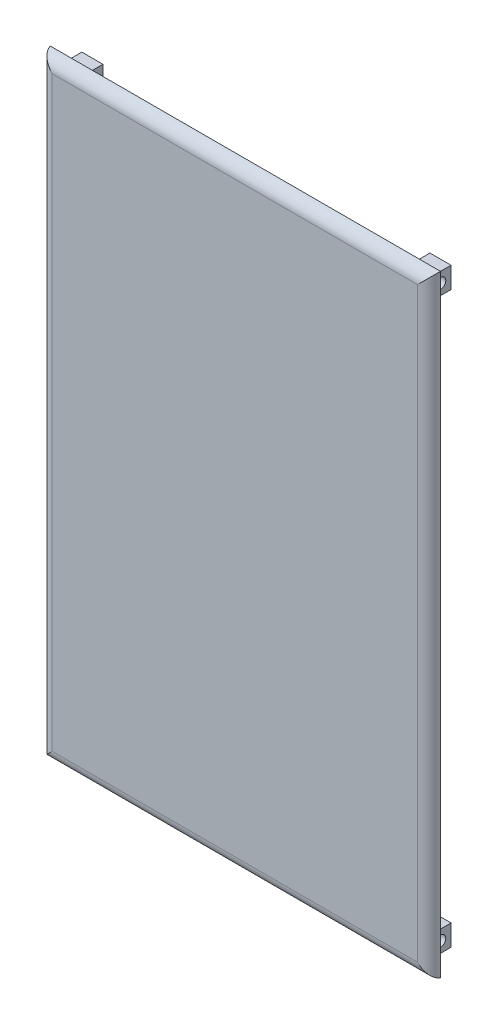
SolidWorks part; units mm, degrees
ref_plane "Front Plane" through (0, 0, 0) normal (0, 0, 1) x (1, 0, 0)
ref_plane "Top Plane" through (0, 0, 0) normal (0, 1, 0) x (1, 0, 0)
ref_plane "Right Plane" through (0, 0, 0) normal (1, 0, 0) x (0, 0, -1)
sketch "Sketch3" plane through (0, 0, 0) normal (0, 0, 1) x (1, 0, 0)
  line L1 (0, 184.15) -> (117.475, 184.15)
  line L2 (0, 184.15) -> (0, 0)
  line L3 (0, 0) -> (117.475, 0)
  line L4 (117.475, 184.15) -> (117.475, 0)
  dimension "D1" = 184.15
  dimension "D2" = 117.475
extrude "Boss-Extrude2" add sketch "Sketch3" along normal blind 3.175
fillet "Fillet1" radius 3.81 4 edges at (58.7375, 0, 3.175) (117.475, 92.075, 3.175) (0, 92.075, 3.175) (58.7375, 184.15, 3.175)
sketch "Sketch13" plane through (0, 0, 0) normal (0, 0, -1) x (-1, 0, 0)
  line L0 (-117.475, 0) -> (-117.475, 184.15) construction
  line L1 (-114.3, 180.975) -> (-3.175, 180.975)
  line L2 (-114.3, 180.975) -> (-114.3, 3.175)
  line L3 (-114.3, 3.175) -> (-3.175, 3.175)
  line L4 (-3.175, 180.975) -> (-3.175, 3.175)
  line L5 (0, 0) -> (-117.475, 0) construction
  line L7 (-112.7125, 179.3875) -> (-4.7625, 179.3875)
  line L8 (-112.7125, 179.3875) -> (-112.7125, 4.7625)
  line L9 (-112.7125, 4.7625) -> (-4.7625, 4.7625)
  line L10 (-4.7625, 179.3875) -> (-4.7625, 4.7625)
  dimension "D1" = 177.8
  dimension "D2" = 111.125
  dimension "D3" = 3.175
  dimension "D4" = 3.175
  dimension "D5" = 174.625
  dimension "D6" = 107.95
  dimension "D7" = 4.7625
  dimension "D8" = 4.7625
extrude "Boss-Extrude4" add sketch "Sketch13" along normal blind 3.175
sketch "Sketch14" plane through (0, 0, 0) normal (0, 0, -1) x (-1, 0, 0)
  line L1 (-114.3, 180.975) -> (-107.95, 180.975)
  line L2 (-114.3, 180.975) -> (-114.3, 174.625)
  line L3 (-114.3, 174.625) -> (-107.95, 174.625)
  line L4 (-107.95, 180.975) -> (-107.95, 174.625)
  line L5 (-3.175, 180.975) -> (-9.525, 180.975)
  line L6 (-3.175, 180.975) -> (-3.175, 174.625)
  line L7 (-3.175, 174.625) -> (-9.525, 174.625)
  line L8 (-9.525, 180.975) -> (-9.525, 174.625)
  line L9 (-114.3, 3.175) -> (-107.95, 3.175)
  line L10 (-114.3, 3.175) -> (-114.3, 9.525)
  line L11 (-114.3, 9.525) -> (-107.95, 9.525)
  line L12 (-107.95, 3.175) -> (-107.95, 9.525)
  line L13 (-3.175, 3.175) -> (-9.525, 3.175)
  line L14 (-3.175, 3.175) -> (-3.175, 9.525)
  line L15 (-3.175, 9.525) -> (-9.525, 9.525)
  line L16 (-9.525, 3.175) -> (-9.525, 9.525)
  dimension "D1" = 6.35
  dimension "D2" = 6.35
  dimension "D3" = 6.35
  dimension "D4" = 6.35
  dimension "D5" = 6.35
  dimension "D6" = 6.35
extrude "Boss-Extrude5" add sketch "Sketch14" along normal blind 6.35
fillet "Fillet9" radius 0.381 20 edges at (58.7375, 179.3875, 0) (4.7625, 92.075, 0) (58.7375, 4.7625, 0) (112.7125, 92.075, 0) (107.95, 179.3875, -1.5875) (107.95, 177.0062, 0) (110.3312, 174.625, 0) (112.7125, 174.625, -1.5875) (9.525, 179.3875, -1.5875) (9.525, 177.0062, 0) (7.1437, 174.625, 0) (4.7625, 174.625, -1.5875) (4.7625, 9.525, -1.5875) (7.1437, 9.525, 0) (9.525, 7.1437, 0) (9.525, 4.7625, -1.5875) (107.95, 4.7625, -1.5875) (107.95, 7.1437, 0) (110.3312, 9.525, 0) (112.7125, 9.525, -1.5875)
sketch "Sketch15" plane through (114.3, 0, 0) normal (1, 0, 0) x (0, 0, -1)
  line L0 (0, 180.975) -> (0, 3.175) construction
  line L1 (6.35, 3.175) -> (0, 3.175) construction
  line L2 (6.35, 9.525) -> (6.35, 3.175) construction
  line L4 (6.35, 180.975) -> (0, 180.975) construction
  circle A0 centre (3.175, 177.8) radius 1.5875
  circle A1 centre (3.175, 6.35) radius 1.5875
  circle A2 centre (3.175, 6.35) radius 1.5875
  dimension "D2" = 3.175
  dimension "D6" = 3.175
  dimension "D1" = 3.175
  dimension "D3" = 3.175
  dimension "D4" = 3.175
  dimension "D5" = 3.175
extrude "Cut-Extrude9" cut sketch "Sketch15" against normal blind 6.35 contours A1 | A0 region at (114.3, 177.8, -3.175) region at (114.3, 6.35, -3.175)
sketch "Sketch16" plane through (3.175, 0, 0) normal (-1, 0, 0) x (0, 0, 1)
  line L0 (-6.35, 174.625) -> (-6.35, 180.975) construction
  line L1 (-6.35, 180.975) -> (0, 180.975) construction
  line L2 (-6.35, 3.175) -> (-6.35, 9.525) construction
  line L3 (-6.35, 3.175) -> (0, 3.175) construction
  circle A0 centre (-3.175, 177.8) radius 1.5875
  circle A1 centre (-3.175, 6.35) radius 1.5875
  dimension "D3" = 3.175
  dimension "D6" = 3.175
  dimension "D1" = 3.175
  dimension "D2" = 3.175
  dimension "D4" = 3.175
  dimension "D5" = 3.175
extrude "Cut-Extrude10" cut sketch "Sketch16" against normal blind 6.35
sketch "Sketch17" plane through (0, 0, 0) normal (0, 0, -1) x (-1, 0, 0)
  line L0 (-9.906, 179.3875) -> (-107.569, 179.3875) construction
  line L1 (-103.3145, 177.8) -> (-101.727, 177.8)
  line L2 (-103.3145, 177.8) -> (-103.3145, 120.65)
  line L3 (-103.3145, 120.65) -> (-101.727, 120.65)
  line L4 (-101.727, 177.8) -> (-101.727, 120.65)
  line L5 (-15.748, 177.8) -> (-14.1605, 177.8)
  line L6 (-15.748, 177.8) -> (-15.748, 120.65)
  line L7 (-15.748, 120.65) -> (-14.1605, 120.65)
  line L8 (-14.1605, 177.8) -> (-14.1605, 120.65)
  line L9 (-112.7125, 9.906) -> (-112.7125, 174.244) construction
  line L10 (-4.7625, 9.906) -> (-4.7625, 174.244) construction
  dimension "D1" = 57.15
  dimension "D2" = 1.5875
  dimension "D3" = 1.5875
  dimension "D4" = 57.15
  dimension "D5" = 1.5875
  dimension "D6" = 1.5875
  dimension "D7" = 9.398
  dimension "D8" = 9.398
extrude "Boss-Extrude6" add sketch "Sketch17" along normal blind 4.7625
sketch "Sketch18" plane through (0, 0, 0) normal (0, 0, -1) x (-1, 0, 0)
  line L1 (-103.3145, 120.396) -> (-101.727, 120.396)
  line L2 (-103.3145, 120.396) -> (-103.3145, 63.246)
  line L3 (-103.3145, 63.246) -> (-101.727, 63.246)
  line L4 (-101.727, 120.396) -> (-101.727, 63.246)
  line L5 (-15.748, 120.396) -> (-14.1605, 120.396)
  line L6 (-15.748, 120.396) -> (-15.748, 63.246)
  line L7 (-15.748, 63.246) -> (-14.1605, 63.246)
  line L8 (-14.1605, 120.396) -> (-14.1605, 63.246)
  line L9 (-112.7125, 9.906) -> (-112.7125, 174.244) construction
  line L10 (-103.3145, 120.65) -> (-101.727, 120.65) construction
  line L11 (-15.748, 120.65) -> (-14.1605, 120.65) construction
  line L12 (-4.7625, 9.906) -> (-4.7625, 174.244) construction
  dimension "D1" = 57.15
  dimension "D2" = 1.5875
  dimension "D3" = 1.5875
  dimension "D4" = 57.15
  dimension "D5" = 9.398
  dimension "D6" = 9.398
  dimension "D7" = 0.254
  dimension "D8" = 0.254
extrude "Boss-Extrude7" add sketch "Sketch18" along normal blind 4.7625
